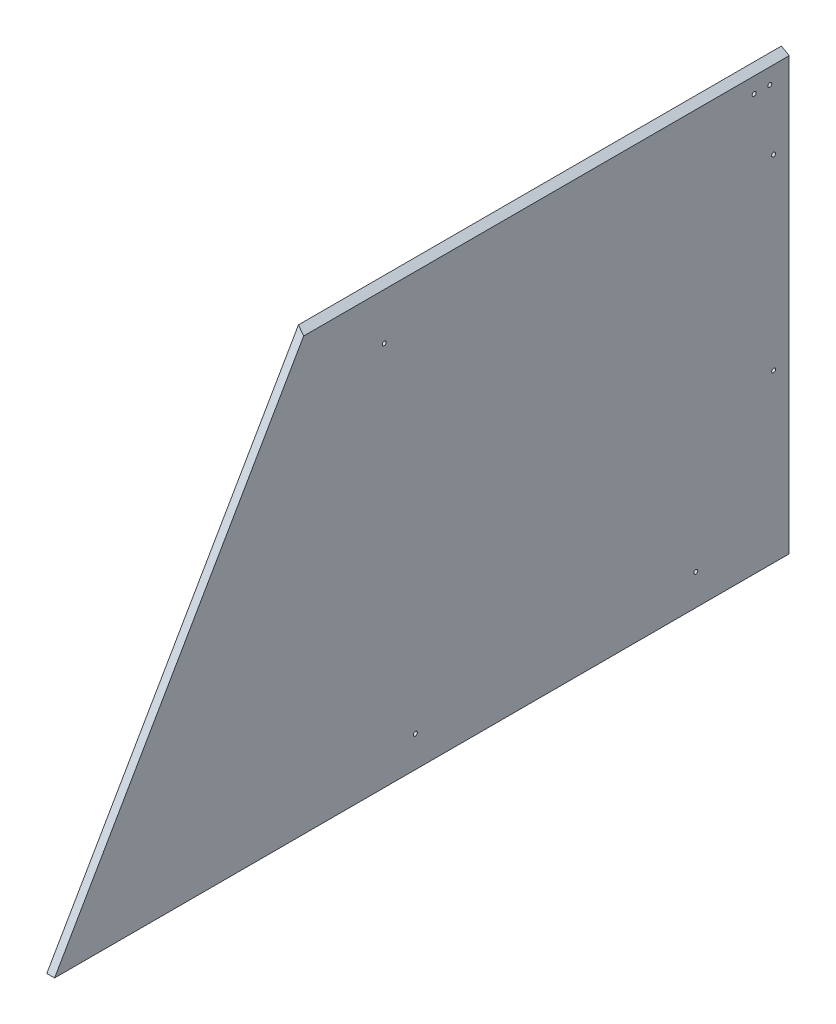
SolidWorks part; units mm, degrees
material "Acrylic (Medium-high impact)"
ref_plane "Front Plane" through (0, 0, 0) normal (0, 0, 1) x (1, 0, 0)
ref_plane "Top Plane" through (0, 0, 0) normal (0, 1, 0) x (1, 0, 0)
ref_plane "Right Plane" through (0, 0, 0) normal (1, 0, 0) x (0, 0, -1)
sketch "Sketch1" plane through (0, 0, 0) normal (1, 0, 0) x (0, 0, -1)
  line L0 (-39.4651, -250.1912) -> (165.8406, 105.4088)
  line L1 (165.8406, 105.4088) -> (559.5406, 105.4088)
  line L3 (-39.4651, -250.1912) -> (559.5406, -250.1912)
  line L4 (559.5406, 105.4088) -> (559.5406, -250.1912)
  dimension "D1" = 60
  dimension "D2" = 355.6
  dimension "D3" = 393.7
extrude "Boss-Extrude1" add sketch "Sketch1" along normal blind 6.35
chamfer "Chamfer1" distance 6.6548 angle 30 1 edges at (6.35, 105.4088, -362.6906) first distance on face at (3.175, 105.4088, -362.6906)
hole_wizard "CSK for #4 Flat Head Machine Screw1" positions "3DSketch1" profile "Sketch2" countersink size "#4" standard "ANSI Inch" end condition through all
sketch3d "3DSketch1"
  line L1 (0, -250.1912, -559.5406) -> (0, 105.2328, -559.5406) construction
  line L2 (0, -250.1912, 39.4651) -> (0, -250.1912, -559.5406) construction
  point P0 (0, 38.0988, -546.8406)
  point P2 (0, 63.4988, -229.3406)
  point P10 (0, -114.3012, -546.8406)
  dimension "D1" = 288.29
  dimension "D2" = 135.89
  dimension "D3" = 330.2
  dimension "D4" = 12.7
  dimension "D5" = 313.69
  dimension "D7" = 12.7
sketch "Sketch2" plane through (0, 38.0988, -546.8406) normal (0, 1, 0) x (0, 0, 1)
  line L0 (0, 0) -> (0, 6.35)
  line L1 (0, 6.35) -> (1.6319, 6.35)
  line L2 (1.6319, 6.35) -> (1.6319, 1.4098)
  line L3 (1.6319, 1.4098) -> (2.8575, 0)
  line L5 (2.8575, 0) -> (0, 0)
  line L6 (-1.6319, 1.4098) -> (-2.8575, 0) construction
  line L11 (0, -6.35) -> (0, 107.95) construction
  dimension "Thru Hole Dia." = 3.2639
  dimension "Thru Hole Depth" = 6.35
  dimension "Near C'Sink Dia." = 5.715
  dimension "Near C'Sink Angle" = 82
hole_wizard "CSK for #4 Flat Head Machine Screw2" positions "Sketch4" profile "Sketch3" countersink size "#4" standard "ANSI Inch" end condition through all
sketch "Sketch4" plane through (0, 0, 0) normal (-1, 0, 0) x (0, 0, 1)
  point P0 (-543.6656, 88.8667)
  point P3 (-530.9656, 88.8667)
sketch "Sketch3" plane through (0, 88.8667, -543.6656) normal (0, 1, 0) x (0, 0, 1)
  line L0 (0, 0) -> (0, 6.35)
  line L1 (0, 6.35) -> (1.6319, 6.35)
  line L2 (1.6319, 6.35) -> (1.6319, 1.4098)
  line L3 (1.6319, 1.4098) -> (2.8575, 0)
  line L5 (2.8575, 0) -> (0, 0)
  line L6 (-1.6319, 1.4098) -> (-2.8575, 0) construction
  line L11 (0, -6.35) -> (0, 107.95) construction
  dimension "Thru Hole Dia." = 3.2639
  dimension "Thru Hole Depth" = 6.35
  dimension "Near C'Sink Dia." = 5.715
  dimension "Near C'Sink Angle" = 82
hole_wizard "CSK for #4 Flat Head Machine Screw3" positions "3DSketch2" profile "Sketch5" countersink size "#4" standard "ANSI Inch" end condition through all
sketch3d "3DSketch2"
  line L0 (0, -250.1912, -559.5406) -> (0, 105.2328, -559.5406) construction
  line L1 (0, -250.1912, 39.4651) -> (0, -250.1912, -559.5406) construction
  point P0 (0, -224.7912, -483.3406)
  point P2 (0, -224.7912, -254.7406)
  dimension "D1" = 76.2
  dimension "D2" = 304.8
  dimension "D3" = 25.4
  dimension "D4" = 25.4
sketch "Sketch5" plane through (0, -224.7912, -483.3406) normal (0, 1, 0) x (0, 0, 1)
  line L0 (0, 0) -> (0, 6.35)
  line L1 (0, 6.35) -> (1.6319, 6.35)
  line L2 (1.6319, 6.35) -> (1.6319, 1.4098)
  line L3 (1.6319, 1.4098) -> (2.8575, 0)
  line L5 (2.8575, 0) -> (0, 0)
  line L6 (-1.6319, 1.4098) -> (-2.8575, 0) construction
  line L11 (0, -6.35) -> (0, 107.95) construction
  dimension "Thru Hole Dia." = 3.2639
  dimension "Thru Hole Depth" = 6.35
  dimension "Near C'Sink Dia." = 5.715
  dimension "Near C'Sink Angle" = 82
